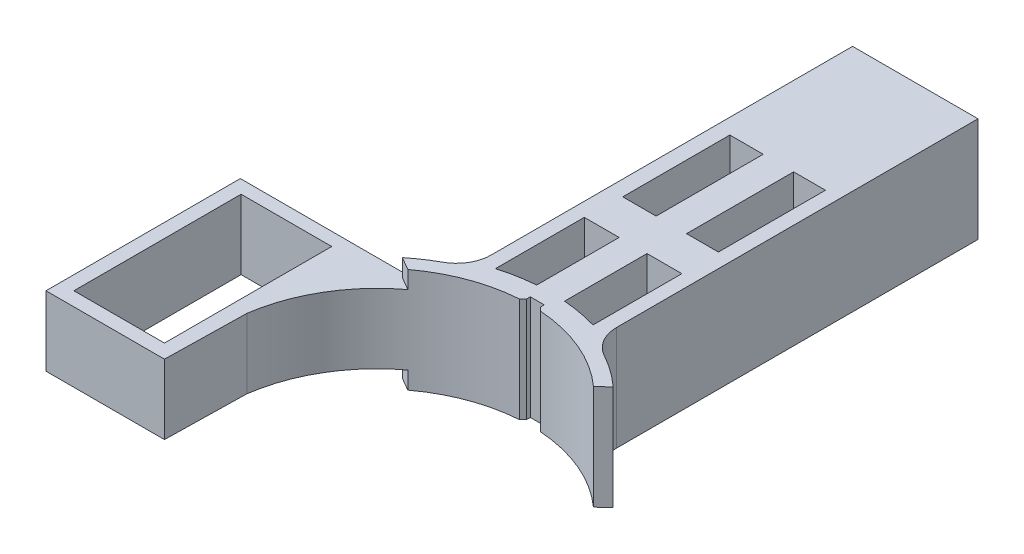
SolidWorks part; units mm, degrees
ref_plane "前视" through (0, 0, 0) normal (0, 0, 1) x (1, 0, 0)
ref_plane "上视" through (0, 0, 0) normal (0, 1, 0) x (1, 0, 0)
ref_plane "右视" through (0, 0, 0) normal (1, 0, 0) x (0, 0, -1)
sketch "草图1" plane through (0, 0, 0) normal (0, 1, 0) x (1, 0, 0)
  line L1 (-5.75, -5.75) -> (5.75, -5.75)
  line L2 (-5.75, -5.75) -> (-5.75, 5.75)
  line L3 (-5.75, 5.75) -> (5.75, 5.75)
  line L4 (5.75, -5.75) -> (5.75, 5.75)
  line L5 (-5.75, -5.75) -> (5.75, 5.75) construction
  line L6 (-5.75, 5.75) -> (5.75, -5.75) construction
  line L7 (-10, -10) -> (10, -10)
  line L8 (-10, -10) -> (-10, 10)
  line L9 (-10, 10) -> (10, 10)
  line L10 (10, -10) -> (10, 10)
  line L11 (-10, -10) -> (10, 10) construction
  line L12 (-10, 10) -> (10, -10) construction
  point P0 (0, 0)
  point P6 (0, 0)
  dimension "D1" = 11.5
  dimension "D2" = 20
extrude "凸台-拉伸1" add sketch "草图1" along normal mid plane 15
sketch "草图3" plane through (-10, 0, 0) normal (-1, 0, 0) x (0, 0, 1)
  line L0 (-10, 7.5) -> (-10, -7.5) construction
  line L1 (-10, -5) -> (-14.4098, -5)
  line L3 (-10, 5) -> (-14.4098, 5)
  line L4 (-10, 5) -> (-10, -5)
  arc A0 (-14.4098, 5) -> (-14.4098, -5) centre (-20, 0) ccw
  point P2 (-10, 0)
  dimension "D3" = 15
  dimension "D1" = 20
  dimension "D2" = 10
  dimension "D4" = 10
  dimension "D5" = 10
extrude "凸台-拉伸2" add sketch "草图3" against normal up to surface (20 mm away) up to face at (10, 0, 0)
sketch "草图4" plane through (0, 7.5, 0) normal (0, 1, 0) x (1, 0, 0)
  line L0 (10, 10) -> (-10, 10) construction
  line L1 (-3.2044, 27.5) -> (2.7956, 27.5)
  line L2 (-3.2044, 27.5) -> (-3.2044, 10)
  line L3 (-3.2044, 10) -> (2.7956, 10)
  line L4 (2.7956, 27.5) -> (2.7956, 10)
  line L5 (-3.2044, 27.5) -> (2.7956, 10) construction
  line L6 (-3.2044, 10) -> (2.7956, 27.5) construction
  line L7 (10, 27.5) -> (-10, 27.5) construction
  point P0 (-0.2044, 18.75)
  dimension "D1" = 6
extrude "切除-拉伸1" cut sketch "草图4" against normal through all
sketch "草图5" plane through (-10, 0, 0) normal (-1, 0, 0) x (0, 0, 1)
  circle A0 centre (-20, 0) radius 2
  dimension "D1" = 4
extrude "切除-拉伸2" cut sketch "草图5" against normal through all
sketch "草图6" plane through (0, 7.5, 0) normal (0, 1, 0) x (1, 0, 0)
  line L0 (-10, -10) -> (10, -10) construction
  line L1 (-9, -10) -> (9, -10)
  line L2 (-9, -10) -> (-9, 27.5)
  line L3 (-9, 27.5) -> (9, 27.5)
  line L4 (9, -10) -> (9, 27.5)
  line L5 (10, 27.5) -> (2.7956, 27.5) construction
  line L6 (10, 14.4098) -> (10, 27.5) construction
  line L7 (-10, 10) -> (-10, -10) construction
  dimension "D1" = 1
  dimension "D2" = 1
extrude "切除-拉伸5" cut sketch "草图6" against normal through all flip side to cut
sketch "草图7" plane through (0, -7.5, 0) normal (0, -1, 0) x (1, 0, 0)
  line L0 (0, 41.0613) -> (0, 10) construction
  line L1 (-9, 10) -> (9, 10) construction
  line L2 (-9, 10) -> (-9, 22.7514)
  line L3 (-9, 10) -> (9, 10)
  line L4 (9, 10) -> (9, 22.7514)
  arc A0 (9, 22.7514) -> (-9, 22.7514) centre (0, 45) ccw
  dimension "D1" = 48
  dimension "D2" = 35
extrude "凸台-拉伸3" add sketch "草图7" against normal up to surface (15 mm away) separate body up to face at (0, 7.5, 0)
sketch "草图10" plane through (0, 7.5, 0) normal (0, 1, 0) x (1, 0, 0)
  line L0 (0, -23) -> (0, 0) construction
  line L1 (-13.1842, -27.3881) -> (-20.7846, -23)
  line L2 (14.6773, -28.6116) -> (20.7846, -23)
  arc A0 (14.6773, -28.6116) -> (-13.1842, -27.3881) centre (0, -45) ccw
  arc A1 (-20.7846, -23) -> (20.7846, -23) centre (0, -45) ccw
  dimension "D1" = 44
  dimension "D2" = 60
extrude "切除-拉伸6" cut sketch "草图10" against normal through all
combine bodies "组合1" operation type add bodies to combine 106 108
sketch "草图11" plane through (0, 7.5, 0) normal (0, 1, 0) x (1, 0, 0)
  line L0 (-7, -8.25) -> (7, -8.25)
  line L2 (7, -8.25) -> (7, -21)
  line L3 (-5.75, -5.75) -> (5.75, -5.75) construction
  line L5 (0, -5.75) -> (0, -14.3067) construction
  line L6 (-7, -8.25) -> (-7, -21)
  arc A0 (7, -21) -> (-7, -21) centre (0, -45) ccw
  dimension "D2" = 25
  dimension "D1" = 2.5
  dimension "D3" = 7
extrude "切除-拉伸9" cut sketch "草图11" against normal through all
sketch "草图12" plane through (0, 7.5, 0) normal (0, 1, 0) x (1, 0, 0)
  line L0 (0, -8.25) -> (0, -16.6119) construction
  line L1 (-1, -24) -> (-1, -22)
  line L2 (-1, -22) -> (1, -22)
  line L3 (1, -22) -> (1, -24)
  line L4 (1, -24) -> (-1, -24)
  line L5 (7, -8.25) -> (-7, -8.25) construction
  arc A1 (7, -21) -> (-7, -21) centre (0, -45) ccw construction
  dimension "D3" = 23
  dimension "D1" = 1
  dimension "D2" = 2
  dimension "D4" = 2
extrude "切除-拉伸10" cut sketch "草图12" against normal blind 16
sketch "草图13" plane through (0, -7.5, 0) normal (0, -1, 0) x (1, 0, 0)
  line L0 (-2, 20.0801) -> (-2, 8.25)
  line L1 (7, 8.25) -> (-7, 8.25) construction
  line L2 (0, 20) -> (0, 8.25) construction
  line L3 (2, 20.0801) -> (2, 8.25)
  line L4 (2, 8.25) -> (-2, 8.25)
  arc A0 (-7, 21) -> (7, 21) centre (0, 45) ccw construction
  arc A1 (-2, 20.0801) -> (2, 20.0801) centre (0, 45) ccw
  dimension "D1" = 2
extrude "凸台-拉伸4" add sketch "草图13" against normal up to surface (15 mm away) up to face at (0, 7.5, 14.375)
sketch "草图14" plane through (0, 0, 0) normal (0, 1, 0) x (1, 0, 0)
  line L0 (-20, -45) -> (22, -45) construction
  line L2 (-37.0004, -27.5) -> (-37.0004, -51.5)
  line L3 (-24.0004, -51.5) -> (-24.0004, -27.5)
  line L4 (-39.0004, -25.609) -> (-10.3918, -25.609)
  line L5 (-39.0004, -25.609) -> (-39.0004, -53.5)
  line L6 (-37.0004, -27.5) -> (-37.0004, -41.8488) construction
  line L7 (-1.9981, -25.5376) -> (-37.0004, -27.5) construction
  line L8 (-39.0004, -25.609) -> (-39.0004, -41.8488) construction
  line L9 (-39.0004, -53.5) -> (-22.001, -53.5)
  line L10 (-2.1101, -23.5408) -> (-39.0004, -25.609) construction
  line L12 (-37.0004, -27.5) -> (-24.0004, -27.5)
  line L13 (-22.001, -53.5) -> (-21.7748, -41.8603)
  line L15 (-37.0004, -51.5) -> (-24.0004, -51.5)
  arc A0 (-10.3918, -25.609) -> (-21.7748, -41.8603) centre (0, -45) ccw construction
  arc A1 (20, -45) -> (-20, -45) centre (0, -45) ccw construction
  circle A2 centre (-30.5004, -45) radius 6.5 construction
  circle A3 centre (0, -45) radius 20 construction
  arc A4 (-10.3918, -25.609) -> (-21.7748, -41.8603) centre (0, -45) ccw construction
  arc A5 (-10.3918, -25.609) -> (-21.7748, -41.8603) centre (0, -45) ccw
  dimension "D1" = 40
  dimension "D2" = 44
  dimension "D3" = 2
  dimension "D6" = 24
  dimension "D7" = 13
  dimension "D4" = 13
  dimension "D5" = 2
extrude "凸台-拉伸5" add sketch "草图14" against normal mid plane 10
fillet "圆角3" radius 5 2 edges at (9, 0, 22.7514) (-9, 0, 22.7514)
chamfer "倒角1" distance 0.5 angle 45 2 edges at (-1, 0, 23.0227) (1, 0, 23.0227) first distance on face at (-1, 0, 22.5114) first distance on face at (1, 0, 22.5114)
sketch "草图15" plane through (0, 7.5, 0) normal (0, 1, 0) x (1, 0, 0)
  line L0 (-5.75, -5.75) -> (20.0305, -5.75)
  line L1 (20.0305, -5.75) -> (22.2026, 33.9274)
  line L2 (22.2026, 33.9274) -> (-42.5036, 32.063)
  line L3 (-42.5036, 32.063) -> (-42.5036, 30.6372)
  line L4 (-36.9104, 4.316) -> (-42.5036, 30.6372)
  line L5 (-36.9104, 4.316) -> (-9, -5.75)
  line L6 (-9, 10) -> (-9, -19.6031) construction
  line L7 (-9, -5.75) -> (-5.75, -5.75)
extrude "切除-拉伸11" cut sketch "草图15" against normal blind 64
sketch "草图16" plane through (0, 0, 5.75) normal (0, 0, -1) x (-1, 0, 0)
  line L4 (-9, -7.5) -> (9, -7.5)
  line L5 (9, -7.5) -> (9, 7.5)
  line L6 (9, 7.5) -> (-9, 7.5)
  line L7 (-9, 7.5) -> (-9, -7.5)
  line L8 (-9, -7.5) -> (9, -7.5)
  line L9 (9, -7.5) -> (9, 7.5)
  line L10 (9, 7.5) -> (-9, 7.5)
  line L11 (-9, 7.5) -> (-9, -7.5)
  dimension "D1" = 0
extrude "凸台-拉伸6" add sketch "草图16" along normal blind 3
sketch "草图17" plane through (0, 0, 2.75) normal (0, 0, -1) x (-1, 0, 0)
  line L4 (-9, 7.5) -> (9, 7.5)
  line L5 (-9, 7.5) -> (-9, -7.5)
  line L6 (-9, -7.5) -> (9, -7.5)
  line M2 (-9, 7.5) -> (-9, -7.5)
  line M3 (-9, -7.5) -> (9, -7.5)
  line M4 (9, -7.5) -> (9, 7.5)
  line M5 (9, 7.5) -> (-9, 7.5)
extrude "凸台-拉伸7" add sketch "草图17" along normal blind 35 contours M5 M2 M3 M4 region at (0, 0, 2.75)
sketch "草图18" plane through (0, -7.5, 0) normal (0, -1, 0) x (1, 0, 0)
  line L1 (6.9351, 2.9414) -> (2.3641, 2.9414)
  line L2 (6.9351, 2.9414) -> (6.9351, -12.4264)
  line L3 (6.9351, -12.4264) -> (2.3641, -12.4264)
  line L4 (2.3641, 2.9414) -> (2.3641, -12.4264)
  line L5 (-2, 2.9414) -> (-6.7871, 2.9414)
  line L6 (-2, 2.9414) -> (-2, -12.4264)
  line L7 (-2, -12.4264) -> (-6.7871, -12.4264)
  line L8 (-6.7871, 2.9414) -> (-6.7871, -12.4264)
extrude "切除-拉伸12" cut sketch "草图18" against normal blind 66
sketch "草图19" plane through (0, 0, -32.25) normal (0, 0, -1) x (-1, 0, 0)
  line L0 (0, 7.5) -> (0, -7.5) construction
  line L1 (9, 7.5) -> (-9, 7.5) construction
  line L2 (-9, -7.5) -> (9, -7.5) construction
  line L3 (-9, 0) -> (9, 0) construction
  line L4 (-9, 7.5) -> (-9, -7.5) construction
  line L5 (9, -7.5) -> (9, 7.5) construction
  circle A0 centre (-4, 4) radius 2
  circle A1 centre (4, 4) radius 2
  circle A2 centre (4, -4) radius 2
  circle A3 centre (12, 4) radius 2 [skipped]
  circle A4 centre (-4, -4) radius 2
  dimension "D1" = 4
  dimension "D3" = 4
  dimension "D2" = 3
extrude "切除-拉伸13" cut sketch "草图19" against normal blind 16
